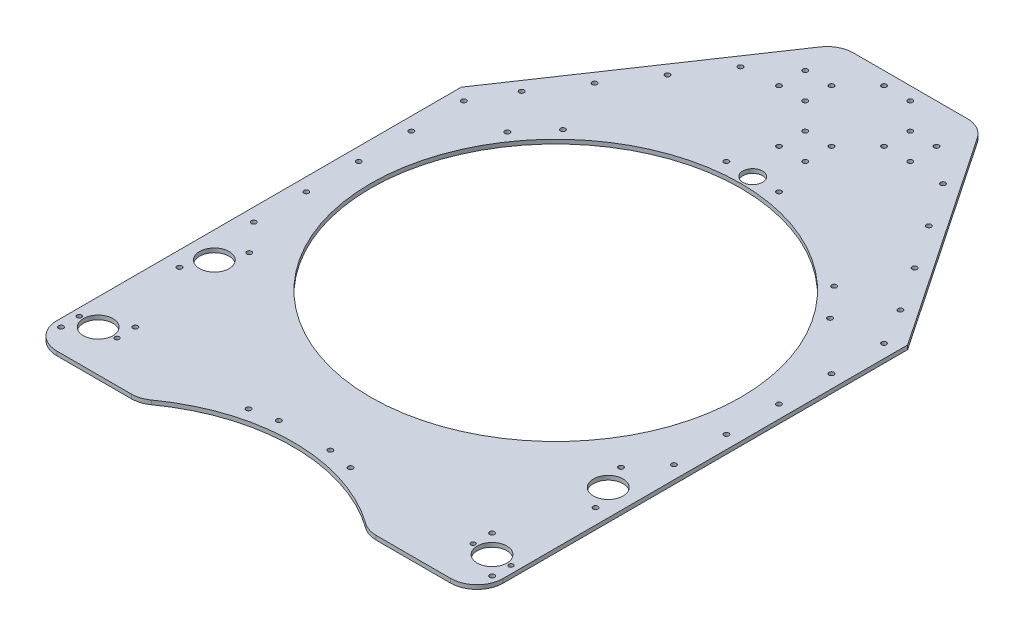
SolidWorks part; units mm, degrees
material "Thornel Mat VMA"
ref_plane "Front Plane" through (0, 0, 0) normal (0, 0, 1) x (1, 0, 0)
ref_plane "Top Plane" through (0, 0, 0) normal (0, 1, 0) x (1, 0, 0)
ref_plane "Right Plane" through (0, 0, 0) normal (1, 0, 0) x (0, 0, -1)
sketch "Sketch1" plane through (0, 0, 0) normal (0, 1, 0) x (1, 0, 0)
  line L1 (-215.9, 342.9) -> (215.9, 342.9)
  line L2 (-215.9, 342.9) -> (-215.9, -342.9)
  line L3 (-215.9, -342.9) -> (215.9, -342.9)
  line L4 (215.9, 342.9) -> (215.9, -342.9)
  line L5 (-215.9, 342.9) -> (215.9, -342.9) construction
  line L6 (-215.9, -342.9) -> (215.9, 342.9) construction
  point P0 (0, 0)
  dimension "D1" = 431.8
  dimension "D2" = 685.8
extrude "Boss-Extrude1" add sketch "Sketch1" along normal blind 4
sketch "Sketch2" plane through (0, 4, 0) normal (0, 1, 0) x (1, 0, 0)
  line L0 (0, -342.9) -> (0, 342.9) construction
  line L1 (-215.9, -342.9) -> (215.9, -342.9) construction
  line L2 (215.9, 342.9) -> (-215.9, 342.9) construction
  line L3 (-215.9, 342.9) -> (-215.9, -342.9) construction
  line L4 (-208.4605, -320.8555) -> (-190.5, -302.895) construction
  line L5 (-193.1461, -302.895) -> (-215.9, -302.895) construction
  line L6 (190.5, -215.9) -> (190.5, -165.1) construction
  line L7 (190.5, -190.5) -> (201.2345, -213.5202) construction
  line L8 (201.2345, -213.5202) -> (179.7655, -167.4798) construction
  line L9 (-208.4605, -320.8555) -> (-172.5395, -284.9345) construction
  circle A0 centre (-190.5, -302.895) radius 14.3129
  circle A1 centre (-190.5, -190.5) radius 14.3129
  circle A3 centre (190.5, -190.5) radius 14.3129
  circle A4 centre (190.5, -190.5) radius 25.4 construction
  circle A5 centre (-190.5, -190.5) radius 25.4 construction
  circle A6 centre (201.2345, -213.5202) radius 2.3812
  circle A7 centre (179.7655, -167.4798) radius 2.3813
  circle A10 centre (-190.5, -302.895) radius 25.4 construction
  circle A11 centre (-208.4605, -320.8555) radius 2.3813
  circle A15 centre (-172.5395, -284.9345) radius 2.3813
  circle A16 centre (172.5395, -284.9345) radius 2.3813
  circle A17 centre (208.4605, -320.8555) radius 2.3813
  circle A18 centre (190.5, -302.895) radius 14.3129
  circle A19 centre (-179.7655, -167.4798) radius 2.3813
  circle A20 centre (-201.2345, -213.5202) radius 2.3813
  circle A21 centre (208.788, -302.895) radius 2.159
  circle A22 centre (172.212, -302.895) radius 2.159
  circle A23 centre (-172.212, -302.895) radius 2.159
  circle A24 centre (-208.788, -302.895) radius 2.159
  point P33 (-190.5, -304.8)
  point P34 (-189.5475, -303.8475)
  point P48 (190.5, -302.895)
  dimension "D1" = 28.6258
  dimension "D2" = 28.6258
  dimension "D6" = 50.8
  dimension "D7" = 50.8
  dimension "D8" = 4.7625
  dimension "D9" = 4.7625
  dimension "D10" = 18.288
  dimension "D11" = 4.318
  dimension "D12" = 50.8
  dimension "D13" = 4.7625
  dimension "D3" = 40.005
  dimension "D4" = 112.395
  dimension "D5" = 25.4
  dimension "D15" = 45
  dimension "D16" = 25
  dimension "D14" = 2
  dimension "D17" = 2
extrude "Cut-Extrude1" cut sketch "Sketch2" against normal through all
sketch "Sketch3" plane through (0, 0, 0) normal (0, -1, 0) x (-1, 0, 0)
  line L1 (29.8706, 270.2084) -> (-24.7394, 270.2084)
  line L2 (29.8706, 270.2084) -> (29.8706, 216.2334)
  line L3 (29.8706, 216.2334) -> (-24.7394, 216.2334)
  line L4 (-24.7394, 270.2084) -> (-24.7394, 216.2334)
  line L5 (29.8706, 270.2084) -> (-24.7394, 216.2334) construction
  line L6 (29.8706, 216.2334) -> (-24.7394, 270.2084) construction
  point P0 (2.5656, 243.2209)
  dimension "D1" = 53.975
  dimension "D2" = 54.61
extrude "Boss-Extrude2" [suppressed] add sketch "Sketch3" along normal blind 203.2
fillet "Fillet1" [suppressed] radius 20.32
sketch "Sketch4" [suppressed] plane through (0, -203.2, 0) normal (0, -1, 0) x (-1, 0, 0)
  line L0 (-24.7394, 216.2334) -> (29.8706, 216.2334) construction
  line L1 (26.6956, 267.0334) -> (-21.5644, 267.0334)
  line L2 (26.6956, 267.0334) -> (26.6956, 219.4084)
  line L3 (26.6956, 219.4084) -> (-21.5644, 219.4084)
  line L4 (-21.5644, 267.0334) -> (-21.5644, 219.4084)
  line L5 (26.6956, 267.0334) -> (-21.5644, 219.4084) construction
  line L6 (26.6956, 219.4084) -> (-21.5644, 267.0334) construction
  line L7 (29.8706, 270.2084) -> (-24.7394, 270.2084) construction
  line L8 (29.8706, 216.2334) -> (29.8706, 270.2084) construction
  line L9 (-24.7394, 270.2084) -> (-24.7394, 216.2334) construction
  point P0 (2.5656, 243.2209)
  dimension "D1" = 3.175
  dimension "D2" = 3.175
  dimension "D3" = 3.175
  dimension "D4" = 3.175
extrude "Cut-Extrude2" [suppressed] cut sketch "Sketch4" against normal blind 203.2
sketch "Sketch5" [suppressed] plane through (-29.8706, 0, 0) normal (-1, 0, 0) x (0, 0, 1)
  line L0 (-216.2334, -203.2) -> (-216.2334, 0) construction
  line L1 (-216.2334, -203.2) -> (-270.2084, -203.2) construction
  circle A0 centre (-243.2209, -184.15) radius 14.2875
  dimension "D1" = 28.575
  dimension "D2" = 26.9875
  dimension "D3" = 19.05
extrude "Cut-Extrude3" [suppressed] cut sketch "Sketch5" against normal blind 203.2
sketch "Sketch6" plane through (0, 4, 0) normal (0, 1, 0) x (1, 0, 0)
  circle A0 centre (0, -50.8) radius 179.07
  dimension "D1" = 358.14
  dimension "D2" = 50.8
extrude "Cut-Extrude4" cut sketch "Sketch6" against normal through all
sketch "Sketch8" plane through (0, 4, 0) normal (0, 1, 0) x (1, 0, 0)
  circle A0 centre (0, 139.7) radius 9.525
  circle A2 centre (0, 139.7) radius 25.4 construction
  circle A3 centre (25.4, 139.7) radius 2.3813
  circle A4 centre (-25.4, 139.7) radius 2.3813
  dimension "D1" = 19.05
  dimension "D3" = 50.8
  dimension "D4" = 4.7625
  dimension "D5" = 4.7625
  dimension "D2" = 139.7
extrude "Cut-Extrude6" cut sketch "Sketch8" against normal through all
fillet "Fillet2" radius 25.4 2 edges at (215.9, 2, 342.9) (-215.9, 2, 342.9)
sketch "Sketch10" plane through (0, 4, 0) normal (0, 1, 0) x (1, 0, 0)
  line L0 (-215.9, 342.9) -> (-215.9, -317.5) construction
  line L1 (215.9, -317.5) -> (215.9, 342.9) construction
  circle A0 centre (-190.5, 215.9) radius 14.3129
  circle A1 centre (190.5, 215.9) radius 14.3129
  circle A2 centre (-190.5, 215.9) radius 25.4 construction
  circle A3 centre (190.5, 215.9) radius 25.4 construction
  circle A4 centre (190.5, 190.5) radius 2.3813
  circle A5 centre (190.5, 241.3) radius 2.3813
  circle A6 centre (-190.5, 190.5) radius 2.3813
  circle A7 centre (-190.5, 241.3) radius 2.3813
  circle A8 centre (190.5, -190.5) radius 14.3129 construction
  circle A9 centre (-190.5, -190.5) radius 14.3129 construction
  dimension "D1" = 28.6258
  dimension "D2" = 50.8
  dimension "D3" = 28.6258
  dimension "D4" = 50.8
  dimension "D5" = 4.7625
  dimension "D6" = 4.7625
  dimension "D7" = 4.7625
  dimension "D8" = 4.7625
  dimension "D9" = 25.4
  dimension "D10" = 25.4
  dimension "D11" = 406.4
  dimension "D12" = 406.4
extrude "Cut-Extrude8" [suppressed] cut sketch "Sketch10" against normal through all
sketch "Sketch11" plane through (0, 4, 0) normal (0, 1, 0) x (1, 0, 0)
  line L0 (0, -50.8) -> (156.0485, 58.4663) construction
  line L6 (0, 0) -> (0, 139.7) construction
  circle A0 centre (0, -50.8) radius 179.07
  circle A1 centre (0, -50.8) radius 179.07 construction
  circle A2 centre (0, -50.8) radius 184.15
  circle A3 centre (0, -50.8) radius 215.9
  circle A4 centre (156.0485, 58.4663) radius 2.3813
  circle A5 centre (131.1838, 87.3342) radius 2.3813
  circle A6 centre (0, -50.8) radius 190.5 construction
  circle A7 centre (-131.1838, 87.3342) radius 2.3813
  circle A8 centre (-156.0485, 58.4663) radius 2.3813
  dimension "D1" = 368.3
  dimension "D6" = 431.8
  dimension "D7" = 381
  dimension "D9" = 4.7625
  dimension "D10" = 4.7625
  dimension "D2" = 55
  dimension "D8" = 38.1
extrude "Cut-Extrude9" cut sketch "Sketch11" against normal through all contours A4 | A5 | A7 | A8 region at (156.0485, 4, -58.4663) region at (131.1838, 4, -87.3342) region at (-131.1838, 4, -87.3342) region at (-156.0485, 4, -58.4663)
sketch "Sketch13" plane through (0, 4, 0) normal (0, 1, 0) x (1, 0, 0)
  line L0 (-215.9, 342.9) -> (-215.9, -317.5) construction
  line L1 (215.9, 342.9) -> (-215.9, 342.9) construction
  line L2 (0, -342.9) -> (0, 342.9) construction
  line L3 (-190.5, -342.9) -> (190.5, -342.9) construction
  circle A0 centre (-203.2, 317.5) radius 2.3813
  circle A1 centre (-203.2, 266.7) radius 2.3813
  circle A2 centre (-203.2, 215.9) radius 2.3813
  circle A3 centre (-203.2, 165.1) radius 2.3813
  circle A4 centre (-203.2, 114.3) radius 2.3813
  circle A5 centre (-203.2, 63.5) radius 2.3813
  circle A6 centre (-203.2, 12.7) radius 2.3813
  circle A7 centre (-203.2, -38.1) radius 2.3813
  circle A8 centre (-203.2, -88.9) radius 2.3813
  circle A9 centre (-203.2, -139.7) radius 2.3813
  circle A10 centre (203.2, -139.7) radius 2.3813
  circle A11 centre (203.2, 12.7) radius 2.3813
  circle A12 centre (203.2, 63.5) radius 2.3813
  circle A13 centre (203.2, 114.3) radius 2.3813
  circle A14 centre (203.2, 165.1) radius 2.3813
  circle A15 centre (203.2, 266.7) radius 2.3813
  circle A16 centre (203.2, 317.5) radius 2.3813
  circle A17 centre (-25.4, -330.2) radius 2.4664
  circle A20 centre (-50.8, -330.2) radius 2.3078
  circle A21 centre (50.8, -330.2) radius 2.3078
  circle A22 centre (25.4, -330.2) radius 2.4664
  circle A23 centre (203.2, -88.9) radius 2.3813
  circle A24 centre (203.2, -38.1) radius 2.3813
  circle A25 centre (203.2, 215.9) radius 2.3813
  dimension "D1" = 4.7625
  dimension "D2" = 12.7
  dimension "D3" = 25.4
  dimension "D5" = 25.4
  dimension "D6" = 50.8
  dimension "D7" = 12.7
  dimension "D8" = 12.7
  dimension "D4" = 10
extrude "Cut-Extrude10" cut sketch "Sketch13" against normal through all
sketch "Sketch14" plane through (0, 4, 0) normal (0, 1, 0) x (1, 0, 0)
  line L0 (215.9, -317.5) -> (215.9, 342.9) construction
  line L1 (0, -342.9) -> (0, -229.87) construction
  line L2 (-190.5, -342.9) -> (190.5, -342.9) construction
  circle A0 centre (209.55, -245.745) radius 2.3813
  circle A2 centre (0, -50.8) radius 179.07 construction
  circle A3 centre (-209.55, -245.745) radius 2.3813
  circle A4 centre (190.5, -302.895) radius 14.3129 construction
  dimension "D1" = 57.15
  dimension "D3" = 4.7625
  dimension "D2" = 6.35
extrude "Cut-Extrude11" [suppressed] cut sketch "Sketch14" against normal through all
sketch "Sketch16" plane through (0, 4, 0) normal (0, 1, 0) x (1, 0, 0)
  line L0 (215.9, -317.5) -> (215.9, 342.9) construction
  line L1 (-215.9, 342.9) -> (215.9, 342.9)
  line L2 (-215.9, 342.9) -> (-215.9, 292.1)
  line L3 (-215.9, 292.1) -> (215.9, 292.1)
  line L4 (215.9, 342.9) -> (215.9, 292.1)
  dimension "D1" = 50.8
extrude "Cut-Extrude13" cut sketch "Sketch16" against normal through all
sketch "Sketch17" plane through (0, 0, 0) normal (0, -1, 0) x (-1, 0, 0)
  line L0 (0, -482.6) -> (0, 3.1553) construction
  line L1 (0, -482.6) -> (24.8652, -293.7298) construction
  line L2 (0, -482.6) -> (49.305, -298.5911) construction
  circle A0 centre (0, -482.6) radius 177.8
  circle A1 centre (0, -482.6) radius 190.5 construction
  circle A2 centre (24.8652, -293.7298) radius 2.3813
  circle A3 centre (49.305, -298.5911) radius 2.3813
  circle A4 centre (-24.8652, -293.7298) radius 2.3813
  circle A5 centre (-49.305, -298.5911) radius 2.3813
  dimension "D1" = 355.6
  dimension "D3" = 381
  dimension "D6" = 4.7625
  dimension "D7" = 4.7625
  dimension "D2" = 482.6
  dimension "D4" = 7.5
  dimension "D5" = 15
extrude "Cut-Extrude14" cut sketch "Sketch17" against normal through all
fillet "Fillet3" radius 25.4 2 edges at (109.9852, 2, 342.9) (-109.9852, 2, 342.9)
sketch "Sketch18" plane through (0, 4, 0) normal (0, 1, 0) x (1, 0, 0)
  line L0 (-215.9, 292.1) -> (215.9, 292.1) construction
  line L1 (25.4, 215.9) -> (-25.4, 215.9) construction
  line L2 (25.4, 215.9) -> (25.4, 266.7) construction
  line L3 (25.4, 266.7) -> (-25.4, 266.7) construction
  line L4 (-25.4, 215.9) -> (-25.4, 266.7) construction
  line L5 (25.4, 215.9) -> (-25.4, 266.7) construction
  line L6 (25.4, 266.7) -> (-25.4, 215.9) construction
  line L8 (25.4, 215.9) -> (76.2, 215.9) construction
  line L9 (25.4, 215.9) -> (25.4, 266.7) construction
  line L10 (25.4, 266.7) -> (76.2, 266.7) construction
  line L11 (76.2, 215.9) -> (76.2, 266.7) construction
  circle A0 centre (38.1, 228.6) radius 2.3812
  circle A1 centre (63.5, 228.6) radius 2.3813
  circle A2 centre (63.5, 254) radius 2.3813
  circle A3 centre (38.1, 254) radius 2.3813
  circle A4 centre (-12.7, 177.8) radius 2.3813
  circle A5 centre (-12.7, 203.2) radius 2.3813
  circle A6 centre (12.7, 177.8) radius 2.3813
  circle A7 centre (12.7, 203.2) radius 2.3812
  circle A8 centre (-63.5, 254) radius 2.3812
  circle A9 centre (-38.1, 254) radius 2.3813
  circle A10 centre (-63.5, 228.6) radius 2.3813
  circle A11 centre (-38.1, 228.6) radius 2.3813
  circle A12 centre (12.7, 304.8) radius 2.3812
  circle A13 centre (12.7, 279.4) radius 2.3812
  circle A14 centre (-12.7, 304.8) radius 2.3813
  circle A15 centre (-12.7, 279.4) radius 2.3812
  point P0 (0, 241.3)
  point P45 (0, 241.3)
  dimension "D5" = 4.7625
  dimension "D1" = 50.8
  dimension "D2" = 50.8
  dimension "D3" = 50.8
  dimension "D4" = 12.7
  dimension "D6" = 25.4
  dimension "D9" = 50.8
  dimension "D10" = 4
  dimension "D7" = 2
  dimension "D8" = 2
extrude "Cut-Extrude15" cut sketch "Sketch18" against normal through all
chamfer "Chamfer1" distance 147.32 angle 56 1 edges at (215.9, 2, -292.1) first distance on face at (0, 2, -292.1)
chamfer "Chamfer2" distance 147.32 angle 56 1 edges at (-215.9, 2, -292.1) first distance on face at (-73.66, 2, -292.1)
fillet "Fillet4" radius 25.4 2 edges at (68.58, 2, -292.1) (-68.58, 2, -292.1)
sketch "Sketch19" plane through (0, 4, 0) normal (0, 1, 0) x (1, 0, 0)
  line L0 (-76.1321, 280.9035) -> (-215.9, 73.6891) construction
  line L1 (-55.0746, 292.1) -> (55.0746, 292.1) construction
  line L2 (0, 292.1) -> (0, -304.8) construction
  circle A0 centre (-97.9769, 225.806) radius 2.3813
  circle A2 centre (-126.3839, 183.6909) radius 2.3813
  circle A3 centre (-154.7909, 141.5758) radius 2.3813
  circle A4 centre (-183.1979, 99.4607) radius 2.3813
  arc A5 (103.6505, -338.1375) -> (-103.6505, -338.1375) centre (0, -482.6) ccw construction
  circle A6 centre (183.1979, 99.4607) radius 2.3813
  circle A7 centre (154.7909, 141.5758) radius 2.3813
  circle A8 centre (126.3839, 183.6909) radius 2.3812
  circle A9 centre (97.9769, 225.806) radius 2.3813
  dimension "D1" = 12.7
  dimension "D2" = 4.7625
  dimension "D3" = 66.294
  dimension "D4" = 4
extrude "Cut-Extrude16" cut sketch "Sketch19" against normal through all
sketch "Sketch20" plane through (0, 4, 0) normal (0, 1, 0) x (1, 0, 0)
  line L5 (251.0039, -358.5351) -> (-248.9961, -358.5351)
  line L6 (251.0039, -358.5351) -> (251.0039, 241.4649)
  line L7 (251.0039, 241.4649) -> (-248.9961, 241.4649)
  line L8 (-248.9961, -358.5351) -> (-248.9961, 241.4649)
  dimension "D1" = 600
  dimension "D2" = 500
